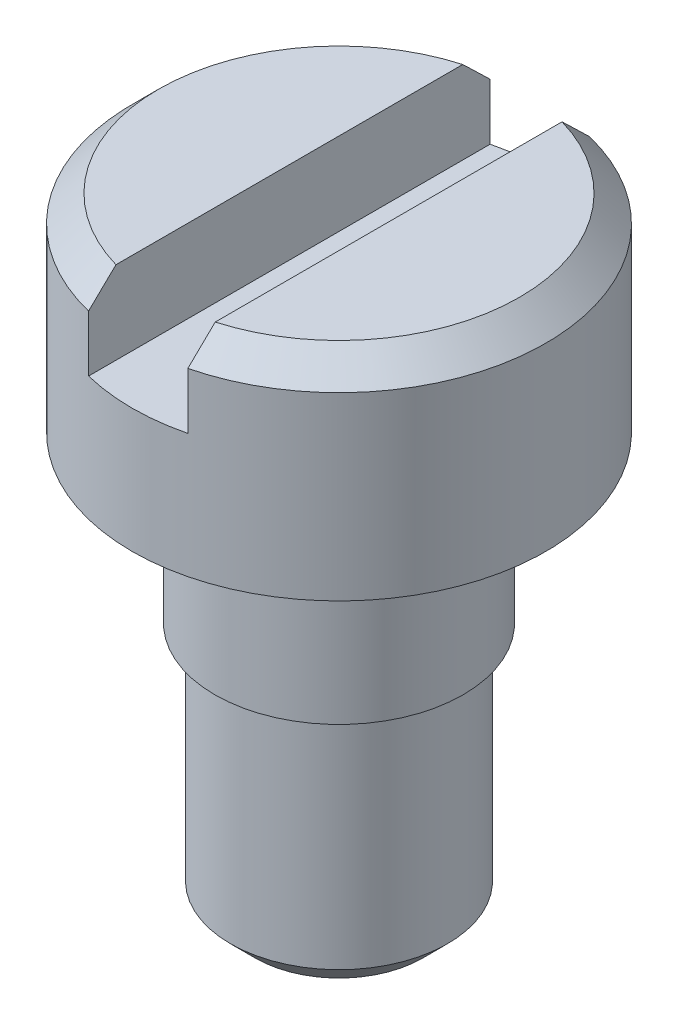
SolidWorks part; units mm, degrees
ref_plane "Front" through (0, 0, 0) normal (0, 0, 1) x (1, 0, 0)
ref_plane "Top" through (0, 0, 0) normal (0, 1, 0) x (1, 0, 0)
ref_plane "Right" through (0, 0, 0) normal (1, 0, 0) x (0, 0, -1)
sketch "Sketch1" plane through (0, 0, 0) normal (0, 1, 0) x (1, 0, 0)
  circle A0 centre (0, 0) radius 3.9688
  point P3 (0, -3.9688)
  dimension "Head Dia" = 7.9375
extrude "Extrude1" add sketch "Sketch1" along normal blind 3.9688
sketch "Sketch2" plane through (0, 3.9688, 0) normal (0, 1, 0) x (-1, 0, 0)
  line L0 (0, 3.9688) -> (0, -3.9688) construction
  line L1 (-0.9525, 3.9688) -> (-0.9525, -3.9688)
  line L2 (0.9525, 3.9688) -> (0.9525, -3.9688)
  line L3 (-0.9525, 3.9688) -> (0.9525, 3.9688)
  line L4 (0.9525, -3.9688) -> (-0.9525, -3.9688)
  circle A0 centre (0, 0) radius 3.9688 construction
  dimension "D1" = 1.905
  dimension "D2" = 0.9525
extrude "Cut-Extrude1" cut sketch "Sketch2" against normal blind 1.5875
sketch "Sketch4" plane through (0, 0, 0) normal (0, -1, 0) x (1, 0, 0)
  circle A0 centre (0, 0) radius 2.3812
  circle A1 centre (0, 0) radius 3.9688 construction
  dimension "Shoulder Dia" = 4.7625
extrude "Extrude2" add sketch "Sketch4" along normal blind 3.175
sketch "Sketch5" plane through (0, -3.175, 0) normal (0, -1, 0) x (1, 0, 0)
  circle A0 centre (0, 0) radius 2.0828
  circle A1 centre (0, 0) radius 2.3812 construction
  point P4 (2.0828, 0)
  dimension "Screw Dia" = 4.1656
extrude "Extrude3" add sketch "Sketch5" along normal blind 4.7625
chamfer "Chamfer1" distance 0.508 angle 45 2 edges at (-3.9688, 3.9688, 0) (3.9688, 3.9688, 0)
chamfer "Chamfer2" distance 0.4763 angle 45 1 edges at (0, -7.9375, -2.0828)
sketch "Sketch7" plane through (0, -7.9375, 0) normal (0, -1, 0) x (1, 0, 0)
  circle A0 centre (0, 0) radius 2.0782
  circle A1 centre (0, 0) radius 2.0828 construction
  dimension "D1" = 4.1563
curve "Helix/Spiral1" pitch 0.7937 height 7.1438 turns 9 parameters "Thread Pitch"=0.7937
sketch "Sketch9" plane through (0, 0, 0) normal (-1, 0, 0) x (0, 0, 1)
  line L0 (-2.0828, -7.9375) -> (-2.0828, -8.632)
  line L1 (-2.0828, -8.632) -> (-1.5672, -8.3344)
  line L2 (-1.5672, -8.3344) -> (-1.5672, -8.2352)
  line L3 (-1.5672, -8.2352) -> (-2.0828, -7.9375)
  line L4 (-1.5672, -8.2848) -> (-2.0828, -8.2848) construction
  line L5 (-1.825, -8.0863) -> (-1.825, -8.4832) construction
  line L8 (-2.0828, -3.175) -> (-2.0828, -7.4613) construction
  line L9 (-1.6066, -7.9375) -> (1.6066, -7.9375) construction
  dimension "D1" = 60
  dimension "D2" = 0.0992
  dimension "D3" = 0.3969
sweep "Cut-Sweep4" [suppressed] cut profiles "Sketch9" path "Helix/Spiral1"
sketch "Sketch10" plane through (0, 0, 0) normal (1, 0, 0) x (0, 0, -1)
  line L0 (-2.3812, -3.175) -> (2.3812, -3.175) construction
  line L1 (0, -3.175) -> (0, -7.9375) construction
  line L2 (-1.6066, -7.9375) -> (1.6066, -7.9375) construction
  line L4 (-2.3812, -3.175) -> (2.3812, -3.175) construction
  line L5 (-1.6066, -7.9375) -> (1.6066, -7.9375) construction
  ellipse E0 centre (0, -5.5563) end of major axis (0, -4.2466) minor radius 0.9592
  dimension "D1" = 2.6194
  dimension "D2" = 1.9184
sketch "Sketch11" plane through (0, 0, 0) normal (1, 0, 0) x (0, 0, -1)
  line L0 (-2.0782, -7.9375) -> (-2.0782, -3.175)
  line L1 (2.0782, -7.9375) -> (2.0782, -3.175)
  line L2 (-2.0782, -7.9375) -> (2.0782, -7.9375) construction
  line L6 (-2.3812, -3.175) -> (2.3812, -3.175) construction
sketch "Sketch12" plane through (0, 3.9688, 0) normal (0, 1, 0) x (1, 0, 0)
  line L0 (-3.9688, 0) -> (3.9688, 0)
  arc A0 (-0.9525, 3.8528) -> (-0.9525, -3.8528) centre (0, 0) ccw construction
  arc A1 (0.9525, -3.8528) -> (0.9525, 3.8528) centre (0, 0) ccw construction
  dimension "hex flats" = 14.2748
  dimension "hex flats/2" = 7.366
equation "\"D1@Cut-Extrude1\"=\"Head Ht@Extrude1\"/2.5"
equation "\"D1@Chamfer2\" = \"Screw Length@Extrude3\" * .1"
equation "\"D3@Helix/Spiral1\" = \"Screw Length@Extrude3\" * 1.5"
equation "\"D1@Sketch7\" = \"Screw Dia@Sketch5\" * .9977678571"
equation "\"D2@Sketch9\" = \"Thread Pitch@Helix/Spiral1\" * .125"
equation "\"D3@Sketch9\" = \"Thread Pitch@Helix/Spiral1\" * .5"
equation "\"D1@Sketch10\" = \"Screw Length@Extrude3\" * .55"
equation "\"D2@Sketch10\" = \"Screw Dia@Sketch5\" * .4605263158"
